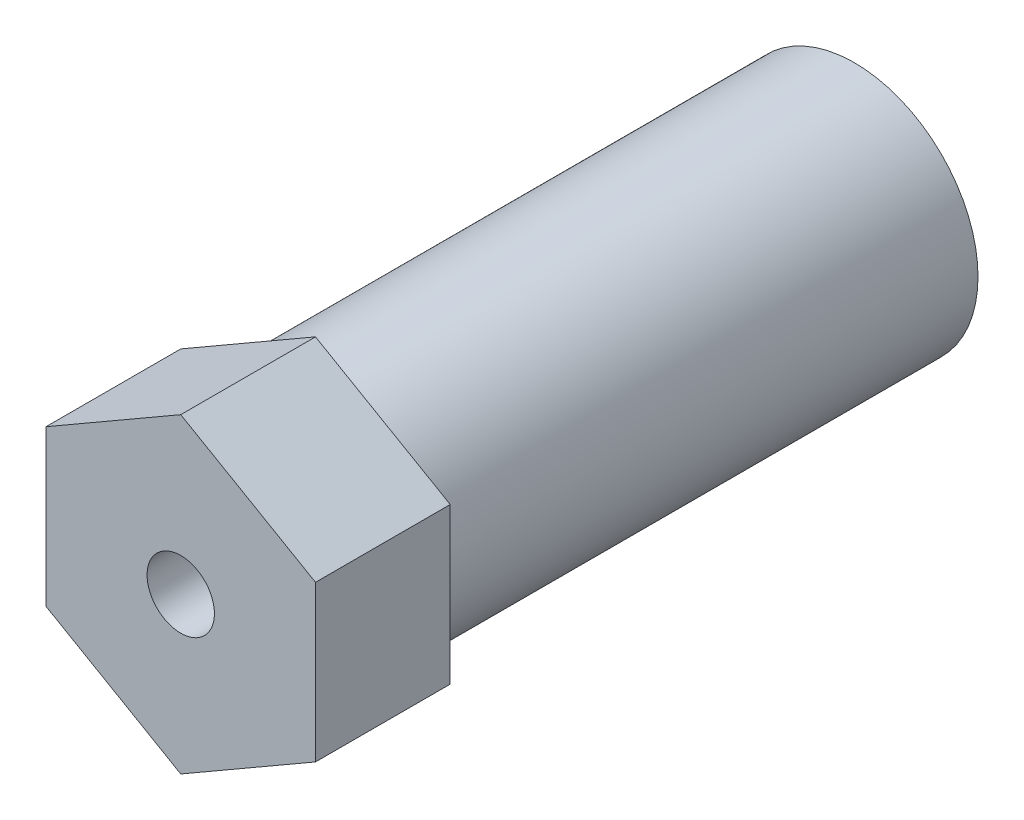
SolidWorks part; units mm, degrees
material "Brass"
ref_plane "Front Plane" through (0, 0, 0) normal (0, 0, 1) x (1, 0, 0)
ref_plane "Top Plane" through (0, 0, 0) normal (0, 1, 0) x (1, 0, 0)
ref_plane "Right Plane" through (0, 0, 0) normal (1, 0, 0) x (0, 0, -1)
sketch "Sketch1" plane through (0, 0, 0) normal (0, 0, 1) x (1, 0, 0)
  line L1 (6, 3.4641) -> (0, 6.9282)
  line L2 (0, 6.9282) -> (-6, 3.4641)
  line L3 (-6, 3.4641) -> (-6, -3.4641)
  line L4 (-6, -3.4641) -> (0, -6.9282)
  line L5 (0, -6.9282) -> (6, -3.4641)
  line L6 (6, -3.4641) -> (6, 3.4641)
  circle A0 centre (0, 0) radius 6 construction
  circle A1 centre (0, 0) radius 5.5
  circle A2 centre (0, 0) radius 1.5
  dimension "D2" = 11
  dimension "D3" = 3
  dimension "D1" = 12
extrude "Boss-Extrude1" add sketch "Sketch1" along normal blind 6 contours A1 | L5 L6 L1 L2 L3 L4 A1 region at (5.8167, 0, 0) region at (-5.3444, 0, 0)
extrude "Boss-Extrude3" add sketch "Sketch1<2>" against normal blind 24 separate body contours A1 region at (-5.3444, 0, 0)
sketch "Sketch1<2>" plane through (0, 0, 0) normal (0, 0, 1) x (1, 0, 0) same geometry as "Sketch1"
sketch "Sketch2" plane through (0, 0, -24) normal (0, 0, -1) x (-1, 0, 0)
  circle A0 centre (0, 0) radius 3
  point P3 (0, 0)
  dimension "D1" = 6
extrude "Cut-Extrude1" cut sketch "Sketch2" against normal blind 25
